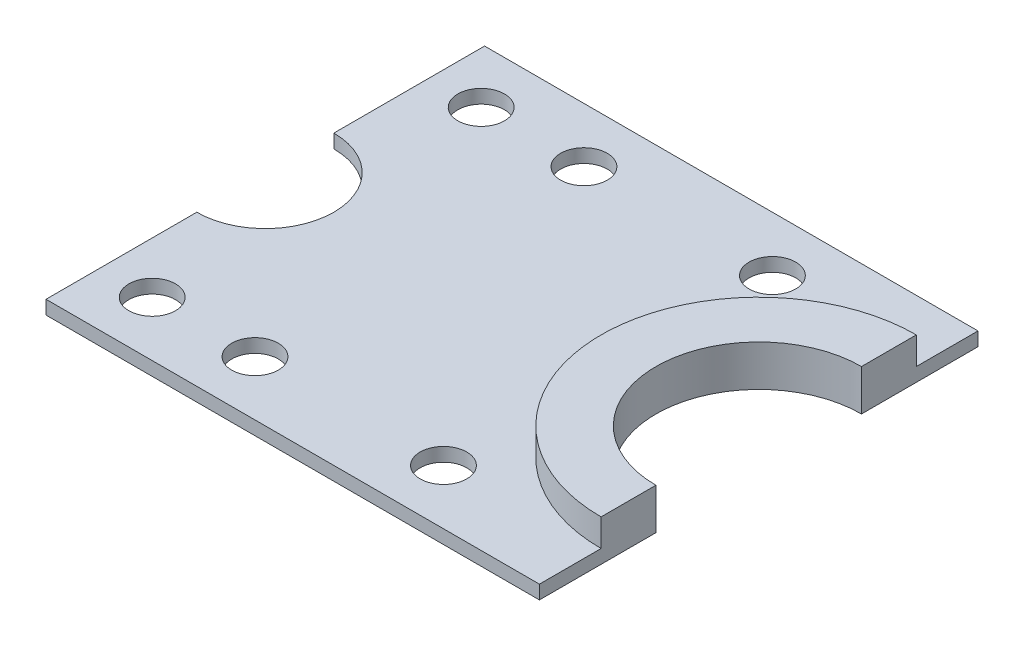
SolidWorks part; units mm, degrees
ref_plane "Front Plane" through (0, 0, 0) normal (0, 0, 1) x (1, 0, 0)
ref_plane "Top Plane" through (0, 0, 0) normal (0, 1, 0) x (1, 0, 0)
ref_plane "Right Plane" through (0, 0, 0) normal (1, 0, 0) x (0, 0, -1)
sketch "Sketch1" plane through (0, 0, 0) normal (0, 1, 0) x (1, 0, 0)
  line L1 (0, 0) -> (36, 0)
  line L2 (0, 0) -> (0, 32)
  line L3 (0, 32) -> (36, 32)
  line L4 (36, 0) -> (36, 32)
  line L5 (0, 0) -> (36, 32) construction
  line L6 (0, 32) -> (36, 0) construction
  point P4 (18, 16)
  dimension "D1" = 36
  dimension "D2" = 32
extrude "Boss-Extrude1" add sketch "Sketch1" along normal blind 1
sketch "Sketch2" plane through (0, 1, 0) normal (0, 1, 0) x (1, 0, 0)
  line L0 (7.5, 28) -> (0, 28) construction
  line L1 (0, 32) -> (15, 32) construction
  line L2 (0, 32) -> (0, 24) construction
  line L3 (0, 24) -> (15, 24) construction
  line L4 (15, 32) -> (15, 24) construction
  line L5 (0, 32) -> (15, 24) construction
  line L6 (0, 24) -> (15, 32) construction
  line L7 (7.5, 28) -> (15, 28) construction
  line L8 (11.25, 28) -> (25, 28) construction
  line L9 (36, 0) -> (36, 32) construction
  line L10 (0, 16) -> (36, 16) construction
  line L11 (0, 32) -> (0, 0) construction
  circle A0 centre (3.75, 28) radius 1.7
  circle A1 centre (11.25, 28) radius 1.7
  circle A2 centre (25, 28) radius 1.7
  circle A3 centre (36, 16) radius 7.5
  circle A4 centre (25, 4) radius 1.7
  circle A5 centre (11.25, 4) radius 1.7
  circle A6 centre (3.75, 4) radius 1.7
  circle A7 centre (0, 16) radius 5
  point P4 (7.5, 28)
  dimension "D3" = 3.4
  dimension "D5" = 15
  dimension "D6" = 10
  dimension "D1" = 15
  dimension "D2" = 8
  dimension "D4" = 13.75
extrude "Cut-Extrude1" cut sketch "Sketch2" against normal up to surface (1 mm away) up to face at (18, 0, -16)
sketch "Sketch3" plane through (0, 1, 0) normal (0, 1, 0) x (1, 0, 0)
  line L0 (36, 23.5) -> (36, 27.5)
  line L1 (36, 8.5) -> (36, 4.5)
  arc A0 (36, 27.5) -> (36, 4.5) centre (36, 16) ccw
  arc A1 (36, 23.5) -> (36, 8.5) centre (36, 16) ccw
  arc A2 (36, 8.5) -> (36, 23.5) centre (36, 16) ccw construction
  arc A3 (36, 4.5) -> (36, 27.5) centre (36, 16) ccw construction
  dimension "D1" = 23
extrude "Boss-Extrude2" add sketch "Sketch3" along normal blind 2
